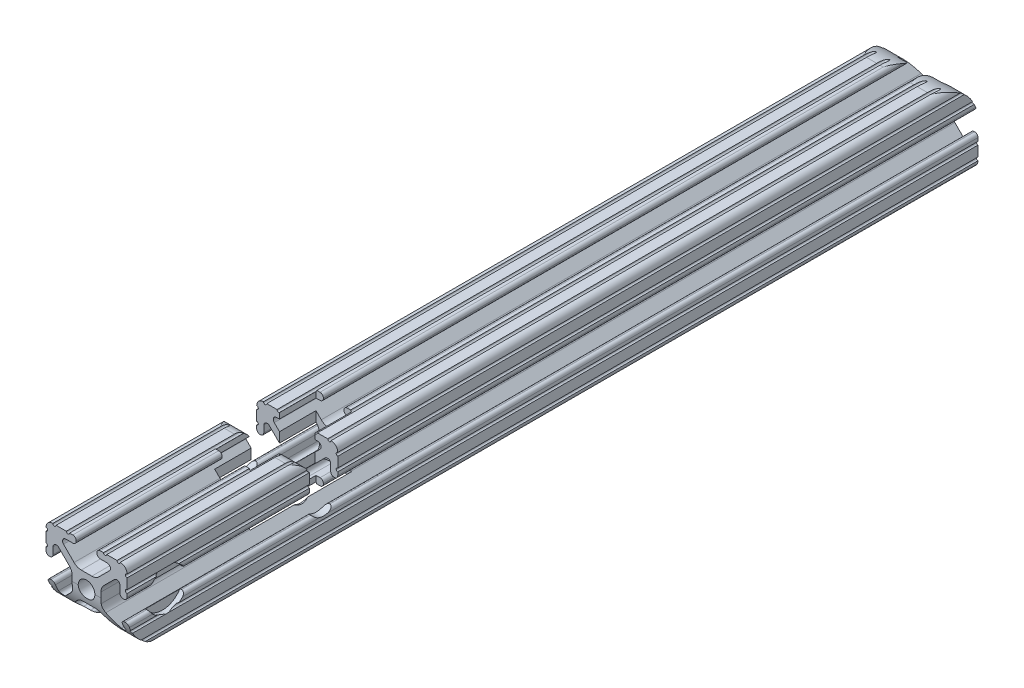
SolidWorks part; units mm, degrees
material "6063-O, Extruded Rod (SS)"
ref_plane "Front Plane" through (0, 0, 0) normal (0, 0, 1) x (1, 0, 0)
ref_plane "Top Plane" through (0, 0, 0) normal (0, 1, 0) x (1, 0, 0)
ref_plane "Right Plane" through (0, 0, 0) normal (1, 0, 0) x (0, 0, -1)
sketch "Sketch1" plane through (0, 0, 0) normal (0, 0, 1) x (1, 0, 0)
  line L88 (-7.1797, -8.6452) -> (-3.9523, -5.4237)
  line L89 (-1.7093, -4.4958) -> (1.7093, -4.4958)
  line L90 (3.9523, -5.4237) -> (7.1797, -8.6452)
  line L91 (6.4164, -10.4902) -> (4.2875, -10.4902)
  line L92 (3.2385, -11.5392) -> (3.2385, -11.651)
  line L93 (4.2875, -12.7) -> (5.3171, -12.7)
  line L94 (6.3331, -12.7) -> (9.5504, -12.7)
  line L95 (12.7, -9.5504) -> (12.7, -6.3331)
  line L96 (12.7, -5.3171) -> (12.7, -4.2875)
  line L97 (11.651, -3.2385) -> (11.5392, -3.2385)
  line L98 (10.4902, -4.2875) -> (10.4902, -6.4021)
  line L99 (8.7371, -7.1294) -> (5.441, -3.8408)
  line L100 (4.5085, -1.5932) -> (4.5085, 1.5932)
  line L101 (5.441, 3.8408) -> (8.7371, 7.1294)
  line L102 (10.4902, 6.4021) -> (10.4902, 4.2875)
  line L103 (11.5392, 3.2385) -> (11.651, 3.2385)
  line L104 (12.7, 4.2875) -> (12.7, 5.3171)
  line L105 (12.7, 6.3331) -> (12.7, 9.5504)
  line L106 (9.5504, 12.7) -> (6.3331, 12.7)
  line L107 (5.3171, 12.7) -> (4.2875, 12.7)
  line L108 (3.2385, 11.651) -> (3.2385, 11.5392)
  line L109 (4.2875, 10.4902) -> (6.4768, 10.4902)
  line L110 (7.207, 8.7244) -> (3.8983, 5.4232)
  line L111 (1.6558, 4.4958) -> (-1.6558, 4.4958)
  line L112 (-3.8983, 5.4232) -> (-7.207, 8.7244)
  line L113 (-6.4768, 10.4902) -> (-4.2875, 10.4902)
  line L114 (-3.2385, 11.5392) -> (-3.2385, 11.651)
  line L115 (-4.2875, 12.7) -> (-5.3171, 12.7)
  line L116 (-6.3331, 12.7) -> (-9.5504, 12.7)
  line L117 (-12.7, 9.5504) -> (-12.7, 6.3331)
  line L118 (-12.7, 5.3171) -> (-12.7, 4.2875)
  line L119 (-11.651, 3.2385) -> (-11.5392, 3.2385)
  line L120 (-10.4902, 4.2875) -> (-10.4902, 6.4021)
  line L121 (-8.7371, 7.1294) -> (-5.441, 3.8408)
  line L122 (-4.5085, 1.5932) -> (-4.5085, -1.5932)
  line L123 (-5.441, -3.8408) -> (-8.7371, -7.1294)
  line L124 (-10.4902, -6.4021) -> (-10.4902, -4.2875)
  line L125 (-11.5392, -3.2385) -> (-11.651, -3.2385)
  line L126 (-12.7, -4.2875) -> (-12.7, -5.3171)
  line L127 (-12.7, -6.3331) -> (-12.7, -9.5504)
  line L128 (-9.5504, -12.7) -> (-6.3331, -12.7)
  line L129 (-5.3171, -12.7) -> (-4.2875, -12.7)
  line L130 (-3.2385, -11.651) -> (-3.2385, -11.5392)
  line L131 (-4.2875, -10.4902) -> (-6.4164, -10.4902)
  circle A1 centre (0, 0) radius 2.6035
  arc A104 (-7.1797, -8.6452) -> (-6.4164, -10.4902) centre (-6.4164, -9.4098) ccw
  arc A105 (-1.7093, -4.4958) -> (-3.9523, -5.4237) centre (-1.7093, -7.6708) ccw
  arc A106 (3.9523, -5.4237) -> (1.7093, -4.4958) centre (1.7093, -7.6708) ccw
  arc A107 (6.4164, -10.4902) -> (7.1797, -8.6452) centre (6.4164, -9.4098) ccw
  arc A108 (4.2875, -10.4902) -> (3.2385, -11.5392) centre (4.2875, -11.5392) ccw
  arc A109 (3.2385, -11.651) -> (4.2875, -12.7) centre (4.2875, -11.651) ccw
  arc A110 (6.3331, -12.7) -> (5.3171, -12.7) centre (5.8251, -12.7) ccw
  arc A111 (10.5664, -12.6998) -> (9.5504, -12.7) centre (10.0584, -12.7) ccw
  arc A112 (10.5664, -12.6998) -> (12.6998, -10.5664) centre (10.5918, -10.5918) ccw
  arc A113 (12.7, -9.5504) -> (12.6998, -10.5664) centre (12.7, -10.0584) ccw
  arc A114 (12.7, -5.3171) -> (12.7, -6.3331) centre (12.7, -5.8251) ccw
  arc A115 (12.7, -4.2875) -> (11.651, -3.2385) centre (11.651, -4.2875) ccw
  arc A116 (11.5392, -3.2385) -> (10.4902, -4.2875) centre (11.5392, -4.2875) ccw
  arc A117 (8.7371, -7.1294) -> (10.4902, -6.4021) centre (9.4628, -6.4021) ccw
  arc A118 (4.5085, -1.5932) -> (5.441, -3.8408) centre (7.6835, -1.5932) ccw
  arc A119 (5.441, 3.8408) -> (4.5085, 1.5932) centre (7.6835, 1.5932) ccw
  arc A120 (10.4902, 6.4021) -> (8.7371, 7.1294) centre (9.4628, 6.4021) ccw
  arc A121 (10.4902, 4.2875) -> (11.5392, 3.2385) centre (11.5392, 4.2875) ccw
  arc A122 (11.651, 3.2385) -> (12.7, 4.2875) centre (11.651, 4.2875) ccw
  arc A123 (12.7, 6.3331) -> (12.7, 5.3171) centre (12.7, 5.8251) ccw
  arc A124 (12.6998, 10.5664) -> (12.7, 9.5504) centre (12.7, 10.0584) ccw
  arc A125 (12.6998, 10.5664) -> (10.5664, 12.6998) centre (10.5918, 10.5918) ccw
  arc A126 (9.5504, 12.7) -> (10.5664, 12.6998) centre (10.0584, 12.7) ccw
  arc A127 (5.3171, 12.7) -> (6.3331, 12.7) centre (5.8251, 12.7) ccw
  arc A128 (4.2875, 12.7) -> (3.2385, 11.651) centre (4.2875, 11.651) ccw
  arc A129 (3.2385, 11.5392) -> (4.2875, 10.4902) centre (4.2875, 11.5392) ccw
  arc A130 (7.207, 8.7244) -> (6.4768, 10.4902) centre (6.4768, 9.4563) ccw
  arc A131 (1.6558, 4.4958) -> (3.8983, 5.4232) centre (1.6558, 7.6708) ccw
  arc A132 (-3.8983, 5.4232) -> (-1.6558, 4.4958) centre (-1.6558, 7.6708) ccw
  arc A133 (-6.4768, 10.4902) -> (-7.207, 8.7244) centre (-6.4768, 9.4563) ccw
  arc A134 (-4.2875, 10.4902) -> (-3.2385, 11.5392) centre (-4.2875, 11.5392) ccw
  arc A135 (-3.2385, 11.651) -> (-4.2875, 12.7) centre (-4.2875, 11.651) ccw
  arc A136 (-6.3331, 12.7) -> (-5.3171, 12.7) centre (-5.8251, 12.7) ccw
  arc A137 (-10.5664, 12.6998) -> (-9.5504, 12.7) centre (-10.0584, 12.7) ccw
  arc A138 (-10.5664, 12.6998) -> (-12.6998, 10.5664) centre (-10.5918, 10.5918) ccw
  arc A139 (-12.7, 9.5504) -> (-12.6998, 10.5664) centre (-12.7, 10.0584) ccw
  arc A140 (-12.7, 5.3171) -> (-12.7, 6.3331) centre (-12.7, 5.8251) ccw
  arc A141 (-12.7, 4.2875) -> (-11.651, 3.2385) centre (-11.651, 4.2875) ccw
  arc A142 (-11.5392, 3.2385) -> (-10.4902, 4.2875) centre (-11.5392, 4.2875) ccw
  arc A143 (-8.7371, 7.1294) -> (-10.4902, 6.4021) centre (-9.4628, 6.4021) ccw
  arc A144 (-4.5085, 1.5932) -> (-5.441, 3.8408) centre (-7.6835, 1.5932) ccw
  arc A145 (-5.441, -3.8408) -> (-4.5085, -1.5932) centre (-7.6835, -1.5932) ccw
  arc A146 (-10.4902, -6.4021) -> (-8.7371, -7.1294) centre (-9.4628, -6.4021) ccw
  arc A147 (-10.4902, -4.2875) -> (-11.5392, -3.2385) centre (-11.5392, -4.2875) ccw
  arc A148 (-11.651, -3.2385) -> (-12.7, -4.2875) centre (-11.651, -4.2875) ccw
  arc A149 (-12.7, -6.3331) -> (-12.7, -5.3171) centre (-12.7, -5.8251) ccw
  arc A150 (-12.6998, -10.5664) -> (-12.7, -9.5504) centre (-12.7, -10.0584) ccw
  arc A151 (-12.6998, -10.5664) -> (-10.5664, -12.6998) centre (-10.5918, -10.5918) ccw
  arc A152 (-9.5504, -12.7) -> (-10.5664, -12.6998) centre (-10.0584, -12.7) ccw
  arc A153 (-5.3171, -12.7) -> (-6.3331, -12.7) centre (-5.8251, -12.7) ccw
  arc A154 (-4.2875, -12.7) -> (-3.2385, -11.651) centre (-4.2875, -11.651) ccw
  arc A155 (-3.2385, -11.5392) -> (-4.2875, -10.4902) centre (-4.2875, -11.5392) ccw
extrude "Boss-Extrude1" add sketch "Sketch1" along normal mid plane 266.7
sketch "Sketch2" plane through (4.5085, 0, 0) normal (1, 0, 0) x (0, 0, -1)
  line L0 (-133.35, -1.5932) -> (-133.35, 1.5932) construction
  line L1 (-133.35, -12.6998) -> (133.35, -12.6998) construction
  circle A0 centre (-120.65, 0) radius 3.175
  dimension "D1" = 6.35
  dimension "D2" = 12.7
  dimension "D3" = 12.6998
extrude "Cut-Extrude1" cut sketch "Sketch2" against normal through all both and the other way through all
sketch "Sketch3" plane through (12.7, 0, 0) normal (1, 0, 0) x (0, 0, -1)
  circle A0 centre (-120.65, 0) radius 6.35
  circle A1 centre (-120.65, 0) radius 3.175 construction
  dimension "D1" = 12.7
extrude "Cut-Extrude2" cut sketch "Sketch3" against normal blind 1.5875
extrude "Cut-Extrude3" cut sketch "Sketch3<2>" along normal blind 1.5875 from surface starting at face at (-12.7, -7.9417, 0)
sketch "Sketch3<2>" plane through (12.7, 0, 0) normal (1, 0, 0) x (0, 0, -1) same geometry as "Sketch3"
sketch "Sketch4" plane through (12.7, 0, 0) normal (1, 0, 0) x (0, 0, -1)
  line L0 (-133.35, 6.3331) -> (-133.35, 9.5504) construction
  line L1 (-133.35, -1.5932) -> (-133.35, 1.5932) construction
  line L2 (-100.0125, 7.62) -> (-100.0125, 12.7)
  line L3 (-100.0125, 12.7) -> (-90.4875, 12.7)
  line L4 (-90.4875, 12.7) -> (-90.4875, 7.62)
  line L5 (-133.35, 12.7) -> (133.35, 12.7) construction
  line L6 (-100.0125, 7.62) -> (-90.4875, 7.62)
  circle A0 centre (-95.25, 7.62) radius 4.7625
  point P6 (-133.35, 0)
  line M4 (-120.1868, 6.3331) -> (133.35, 6.3331)
  line M6 (133.35, 9.5504) -> (-133.35, 9.5504)
  dimension "D3" = 9.525
  dimension "D1" = 38.1
  dimension "D2" = 7.62
extrude "Cut-Extrude4" [suppressed] cut sketch "Sketch4" against normal through all contours A0 L4 L3 L2 M6 | A0 L2 M6 | L6 A0 M6 | A0 M6 | A0 L4 M6 | L6 A0 M4 | A0 M4
sketch "Sketch5" plane through (12.7, 0, 0) normal (1, 0, 0) x (0, 0, -1)
  line L3 (-133.35, -12.7) -> (-120.65, -12.7)
  line L4 (-133.35, -12.7) -> (133.35, -12.7) construction
  line L6 (-133.35, -12.7) -> (-133.35, 0)
  arc A1 (-133.35, 0) -> (-120.65, -12.7) centre (-120.65, 0) ccw
  line M6 (133.35, 9.5504) -> (-133.35, 9.5504)
  line M8 (-133.35, 6.3331) -> (-121.1132, 6.3331)
extrude "Cut-Extrude5" cut sketch "Sketch5" against normal through all contours L3 | M8 | M6 region at (12.7, -9.8632, 130.5132)
sketch "Sketch6" [suppressed] plane through (12.7, 0, 0) normal (1, 0, 0) x (0, 0, -1)
  line L0 (-102.9845, 12.7) -> (-95.25, 12.7)
  line L1 (-100.0125, 12.7) -> (-133.35, 12.7) construction
  line L2 (-95.25, 12.7) -> (-95.25, 12.3825)
  circle A0 centre (-120.65, 0) radius 26.5184 construction
  circle A1 centre (-95.25, 7.62) radius 4.7625
  arc A2 (-91.8477, 4.2875) -> (-91.0813, 5.3171) centre (-95.25, 7.62) ccw construction
  circle A3 centre (-120.65, 0) radius 31.2809 construction
  circle A4 centre (-120.65, 0) radius 21.7568 construction
  arc A5 (-102.9845, 12.7) -> (-99.7865, 6.1704) centre (-120.65, 0) cw
  arc M11 (-99.8353, 6.3331) -> (-100.0125, 7.62) centre (-95.25, 7.62) cw
  line M12 (-100.0125, 7.62) -> (-100.0125, 9.5504)
  line M13 (-100.0125, 9.5504) -> (-133.35, 9.5504)
extrude "Cut-Extrude6" [suppressed] cut sketch "Sketch6" against normal through all contours L0 A5 A1 L2 M13 M12 | A5 M13 M11 M12
sketch "Sketch7" plane through (-12.7, 0, 0) normal (-1, 0, 0) x (0, 0, 1)
  line L0 (-133.35, 1.5932) -> (-133.35, -1.5932) construction
  line L2 (-133.35, 0) -> (-133.35, 12.7)
  line L3 (-133.35, 12.7) -> (-120.65, 12.7)
  line L4 (133.35, 12.7) -> (-133.35, 12.7) construction
  arc A0 (-133.35, 0) -> (-120.65, 12.7) centre (-120.65, 0) cw
extrude "Cut-Extrude7" cut sketch "Sketch7" against normal through all
sketch "Sketch8" plane through (0, -12.7, 0) normal (0, -1, 0) x (1, 0, 0)
  line L0 (12.6998, 127.6957) -> (12.6998, -133.35) construction
  line L1 (-12.7, 133.35) -> (12.6998, 133.35) construction
  line L2 (-12.7, 133.35) -> (-12.7, 41.1809) construction
  line L3 (-12.7, 41.1809) -> (12.6998, 41.1809) construction
  line L4 (12.6998, 133.35) -> (12.6998, 41.1809) construction
  line L5 (-0.0001, 41.1809) -> (-0.0001, 133.35) construction
  line L7 (-5.5563, 87.63) -> (5.5562, 87.63)
  line L8 (-5.5563, 87.63) -> (-5.5563, 55.88)
  line L9 (-5.5563, 55.88) -> (5.5562, 55.88)
  line L10 (5.5562, 87.63) -> (5.5562, 55.88)
  circle A0 centre (-0.0001, 100.33) radius 3.175 construction
  circle A1 centre (-0.0001, 43.18) radius 3.175
  point P17 (-0.0001, 87.63)
  point P18 (5.5562, 82.8245)
  dimension "D1" = 6.35
  dimension "D2" = 12.7
  dimension "D3" = 12.7
  dimension "D4" = 31.75
  dimension "D5" = 11.1125
  dimension "D6" = 33.02
extrude "Cut-Extrude8" cut sketch "Sketch8" against normal through all
sketch "Sketch9" plane through (12.7, 0, 0) normal (1, 0, 0) x (0, 0, -1)
  line L0 (-120.7122, -12.6998) -> (133.35, -12.6998) construction
  line L1 (-87.63, 12.7) -> (-55.88, 12.7)
  line L2 (-87.63, 12.7) -> (-87.63, -12.6998) construction
  line L3 (-87.63, -12.6998) -> (-55.88, -12.6998) construction
  line L4 (-55.88, 12.7) -> (-55.88, -12.6998) construction
  line L5 (-55.88, 1.5932) -> (-55.88, -1.5932) construction
  line L7 (-76.2, 12.7) -> (-67.31, 12.7)
  line L8 (-76.2, 12.7) -> (-76.2, 0.0001)
  line L9 (-76.2, 0.0001) -> (-67.31, 0.0001)
  line L10 (-67.31, 12.7) -> (-67.31, 0.0001)
  circle A0 centre (-71.755, 0.0001) radius 4.445
  circle A1 centre (-80.645, 8.255) radius 4.445
  point P14 (-71.755, 0.0001)
  point P15 (-71.755, 12.7)
  point P17 (-55.88, 0.0001)
  line M9 (-120.1868, 6.3331) -> (131.6583, 6.3331)
  line M11 (129.0214, 9.5504) -> (-133.35, 9.5504)
  dimension "D1" = 8.89
extrude "Cut-Extrude9" cut sketch "Sketch9" against normal through all contours L10 L8 M11 M9 | L10 L7 L8 M11 | A0 L10 L8 M9 | L9 A0 | L9 A0 | A1 L8 L1 M11 region at (12.7, 11.7564, 77.2114) region at (12.7, 11.1252, 71.755) region at (12.7, 7.9417, 71.755) region at (12.7, 4.739, 71.755) region at (12.7, -1.8864, 71.755) region at (12.7, 1.8866, 71.755)
